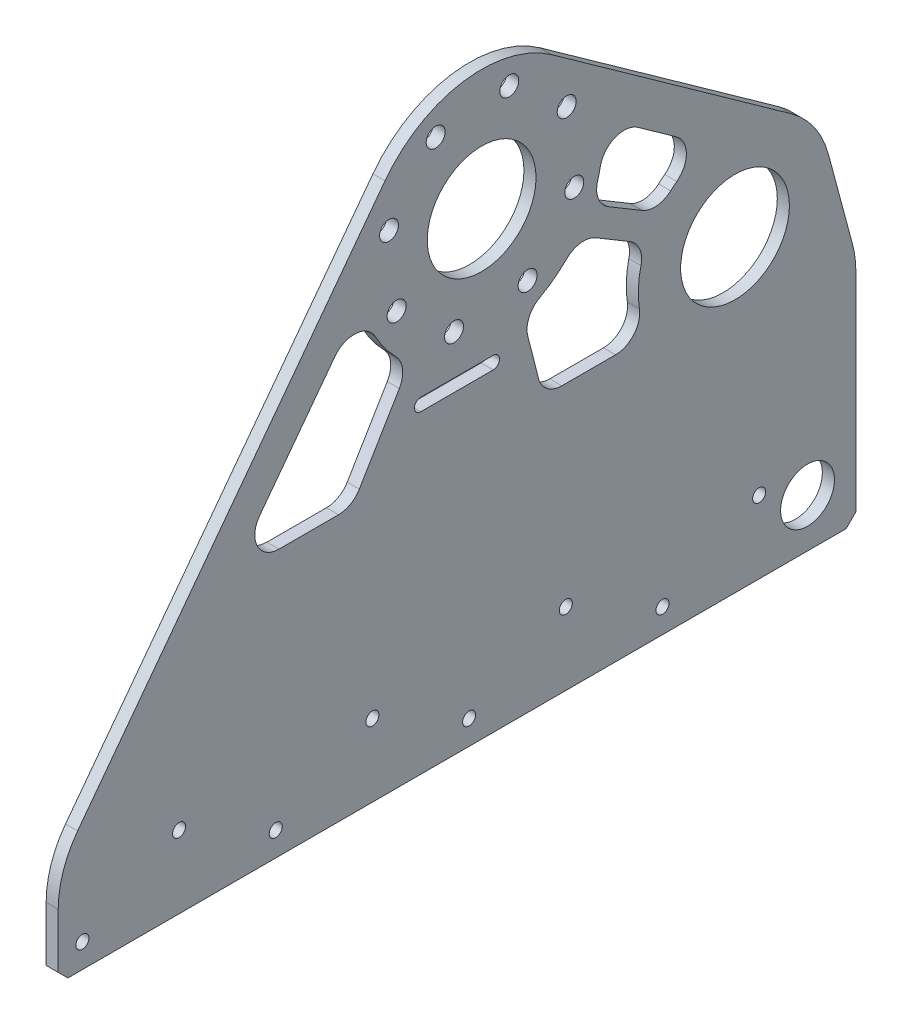
SolidWorks part; units mm, degrees
material "6061-T6 (SS)"
ref_plane "Front Plane" through (0, 0, 0) normal (0, 0, 1) x (1, 0, 0)
ref_plane "Top Plane" through (0, 0, 0) normal (0, 1, 0) x (1, 0, 0)
ref_plane "Right Plane" through (0, 0, 0) normal (1, 0, 0) x (0, 0, -1)
sketch "Sketch1" plane through (0, 0, 0) normal (1, 0, 0) x (0, 0, -1)
  line L0 (0, -25.4) -> (0, 31.864)
  line L13 (-209.55, -25.4) -> (0, -25.4)
  line L14 (-209.55, -25.4) -> (-209.55, -8.4756)
  line L15 (-204.4603, 6.7773) -> (-123.6994, 114.3161)
  line L16 (-209.55, 0) -> (0, 0) construction
  line L17 (-7.2155, 62.1365) -> (-0.8655, 38.438)
  line L18 (-79.8716, 121.0963) -> (-16.9981, 76.2396)
  circle A5 centre (-31.75, 55.5625) radius 14.2875
  circle A6 centre (-98.3115, 95.25) radius 14.2875 construction
  arc A7 (-79.8716, 121.0963) -> (-123.6994, 114.3161) centre (-98.3115, 95.25) ccw
  arc A8 (-16.9981, 76.2396) -> (-7.2155, 62.1365) centre (-31.75, 55.5625) cw
  circle A9 centre (-98.3115, 95.25) radius 14.2875
  arc A10 (-209.55, -8.4756) -> (-204.4603, 6.7773) centre (-184.15, -8.4756) cw
  arc A11 (-0.8655, 38.438) -> (0, 31.864) centre (-25.4, 31.864) cw
  point P4 (0, 0)
  dimension "D4" = 31.75
  dimension "D7" = 25.4
  dimension "D10" = 28.575
  dimension "D3" = 41.275
  dimension "D9" = 25.4
  dimension "D12" = 77.4954
  dimension "D13" = 63.5
  dimension "D14" = 63.5
  dimension "D5" = 25.4
  dimension "D8" = 28.575
  dimension "D2" = 15
  dimension "D6" = 209.55
extrude "Boss-Extrude1" add sketch "Sketch1" along normal blind 3.175
hole_wizard "#10 Clearance Hole1" positions "Sketch2" profile "Sketch3" hole size "#10" standard "ANSI Inch" end condition through all
sketch "Sketch2" plane through (3.175, 0, 0) normal (1, 0, 0) x (0, 0, -1)
  line L0 (-98.3115, 95.25) -> (-31.75, 55.5625) construction
  line L1 (-72.9115, 95.25) -> (-86.2351, 72.9046) construction
  circle A0 centre (-98.3115, 95.25) radius 25.4 construction
  circle A1 centre (-31.75, 55.5625) radius 14.2875 construction
  point P17 (-91.0503, 119.59)
  point P38 (-75.9661, 107.3265)
  point P39 (-73.9716, 87.9887)
  point P40 (-86.2351, 72.9046)
  point P41 (-105.5728, 70.91)
  point P42 (-120.657, 83.1735)
  point P43 (-122.6515, 102.5113)
  point P44 (-110.388, 117.5954)
  dimension "D1" = 50.8
  dimension "D2" = 8
sketch "Sketch3" plane through (3.175, 119.59, 91.0503) normal (0, 1, 0) x (0, 0, -1)
  line L0 (0, 0) -> (0, 3.175)
  line L1 (0, 3.175) -> (2.4892, 3.175)
  line L2 (2.4892, 3.175) -> (2.4892, 0)
  line L5 (2.4892, 0) -> (0, 0)
  line L11 (0, -6.35) -> (0, 107.95) construction
  dimension "Thru Hole Dia." = 4.9784
  dimension "Thru Hole Depth" = 3.175
sketch "Sketch9" plane through (3.175, 0, 0) normal (1, 0, 0) x (0, 0, -1)
  line L0 (0, 0) -> (-208.0942, 0) construction
  line L1 (0, -25.4) -> (0, 31.864) construction
  line L2 (0, -25.4) -> (0, 31.864) construction
  line L3 (-209.55, -25.4) -> (0, -25.4) construction
  line L4 (-164.2565, 44.45) -> (-129.699, 90.4657)
  line L5 (-123.6994, 114.3161) -> (-204.4603, 6.7773) construction
  line L6 (-176.1684, 44.45) -> (-132.2977, 44.45) construction
  line L7 (-164.2565, 44.45) -> (-132.2977, 44.45)
  line L8 (-66.9456, 100.1737) -> (-38.6711, 80.0014)
  line L9 (-16.9981, 76.2396) -> (-79.8716, 121.0963) construction
  line L10 (-69.5519, 81.7985) -> (-51.7692, 71.1955)
  line L11 (-55.0212, 65.7415) -> (-72.8039, 76.3444)
  line L12 (-98.3115, 95.25) -> (-31.75, 55.5625) construction
  line L13 (-98.3115, 95.25) -> (-132.7027, 37.5711) construction
  line L14 (-98.3115, 95.25) -> (-81.8784, 30.2801) construction
  line L15 (-117.2171, 69.7423) -> (-132.2977, 44.45)
  line L16 (-124.9046, 44.45) -> (-111.763, 66.4903) construction
  line L17 (-93.6431, 63.8451) -> (-88.7375, 44.45) construction
  line L18 (-82.1875, 44.45) -> (-87.487, 65.4022)
  line L19 (-82.1875, 44.45) -> (0, 44.45) construction
  line L20 (-82.1875, 44.45) -> (-54.5901, 44.45)
  line L21 (-124.9046, 44.45) -> (-88.7375, 44.45) construction
  line L22 (-124.9046, 44.45) -> (-88.7375, 44.45) construction
  circle A0 centre (-12.7, -12.7) radius 7.0739
  arc A2 (-204.4603, 6.7773) -> (-209.55, -8.4756) centre (-184.15, -8.4756) ccw construction
  arc A3 (-69.5519, 81.7985) -> (-117.2171, 69.7423) centre (-98.3115, 95.25) ccw construction
  arc A4 (-79.8716, 121.0963) -> (-123.6994, 114.3161) centre (-98.3115, 95.25) ccw construction
  arc A5 (-55.0212, 65.7415) -> (-51.7692, 71.1955) centre (-31.75, 55.5625) ccw construction
  arc A6 (-7.2155, 62.1365) -> (-16.9981, 76.2396) centre (-31.75, 55.5625) ccw construction
  arc A7 (-129.699, 90.4657) -> (-117.2171, 69.7423) centre (-98.3115, 95.25) ccw
  arc A8 (-54.5901, 44.45) -> (-55.0212, 65.7415) centre (-31.75, 55.5625) cw
  arc A9 (-51.7692, 71.1955) -> (-38.6711, 80.0014) centre (-31.75, 55.5625) cw
  arc A10 (-69.5519, 81.7985) -> (-66.9456, 100.1737) centre (-98.3115, 95.25) ccw
  arc A11 (-87.487, 65.4022) -> (-72.8039, 76.3444) centre (-98.3115, 95.25) ccw construction
  arc A12 (-87.487, 65.4022) -> (-72.8039, 76.3444) centre (-98.3115, 95.25) ccw
  arc A13 (-111.763, 66.4903) -> (-93.6431, 63.8451) centre (-98.3115, 95.25) ccw construction
  arc A14 (-111.763, 66.4903) -> (-93.6431, 63.8451) centre (-98.3115, 95.25) ccw construction
  dimension "D1" = 14.1478
  dimension "D3" = 12.7
  dimension "D2" = 12.7
  dimension "D4" = 9.525
  dimension "D5" = 44.45
  dimension "D6" = 9.525
  dimension "D7" = 6.35
  dimension "D8" = 6.35
  dimension "D9" = 6.35
  dimension "D10" = 45
  dimension "D11" = 45
extrude "Cut-Extrude1" cut sketch "Sketch9" against normal through all
fillet "Fillet1" radius 6.35 13 edges at (1.5875, 100.1737, 66.9456) (1.5875, 71.1955, 51.7692) (1.5875, 81.7985, 69.5519) (1.5875, 80.0014, 38.6711) (1.5875, 76.3444, 72.8039) (1.5875, 65.7415, 55.0212) (1.5875, 44.45, 82.1875) (1.5875, 65.4022, 87.487) (1.5875, 44.45, 54.5901) (1.5875, 44.45, 164.2565) (1.5875, 90.4657, 129.699) (1.5875, 69.7423, 117.2171) (1.5875, 44.45, 132.2977)
hole_wizard "1/8 (0.135) Diameter Hole1" positions "Sketch10" profile "Sketch11" hole size "1/8" standard "ANSI Inch" end condition through all
sketch "Sketch10" plane through (3.175, 0, 0) normal (1, 0, 0) x (0, 0, -1)
  point P4 (-177.8, -6.35)
  point P7 (-152.4, -19.05)
  point P10 (-127, -6.35)
  point P13 (-101.6, -19.05)
  point P16 (-76.2, -6.35)
  point P19 (-50.8, -19.05)
  point P22 (-25.4, -6.35)
  point P26 (-203.2, -19.05)
sketch "Sketch11" plane through (3.175, -6.35, 177.8) normal (0, 1, 0) x (0, 0, -1)
  line L0 (0, 0) -> (0, 3.175)
  line L1 (0, 3.175) -> (1.7145, 3.175)
  line L2 (1.7145, 3.175) -> (1.7145, 0)
  line L5 (1.7145, 0) -> (0, 0)
  line L11 (0, -6.35) -> (0, 107.95) construction
  dimension "Thru Hole Dia." = 3.429
  dimension "Thru Hole Depth" = 3.175
chamfer "Chamfer1" distance 2.54 angle 45 2 edges at (1.5875, -25.4, 0) (1.5875, -25.4, 209.55)
sketch "Sketch12" plane through (3.175, 0, 0) normal (1, 0, 0) x (0, 0, -1)
  line L0 (-53.34, 60.325) -> (-95.265, 60.325) construction
  line L6 (-114.315, 58.7375) -> (-95.265, 58.7375) construction
  line L8 (-114.315, 60.3885) -> (-95.265, 60.3885)
  line L10 (-96.5799, 60.325) -> (-86.2025, 60.325) construction
  line L11 (-114.315, 57.0865) -> (-95.265, 57.0865)
  line L12 (-95.265, 60.325) -> (-95.265, 57.15) construction
  line L13 (-341.2998, 60.325) -> (-114.315, 60.325) construction
  line L14 (-341.2998, 57.15) -> (-114.315, 57.15) construction
  line L15 (-114.315, 58.7375) -> (-123.7788, 58.7375) construction
  line L16 (-130.4505, 47.548) -> (-119.931, 65.1907) construction
  line L17 (-95.265, 58.7375) -> (-85.8013, 58.7375) construction
  line L18 (-86.1876, 60.2647) -> (-83.3998, 49.2429) construction
  arc A0 (-83.0781, 67.3931) -> (-86.1876, 60.2647) centre (-80.0314, 61.8218) ccw construction
  arc A3 (-114.315, 60.3885) -> (-114.315, 57.0865) centre (-114.315, 58.7375) ccw
  arc A4 (-95.265, 57.0865) -> (-95.265, 60.3885) centre (-95.265, 58.7375) ccw
  point P3 (-104.79, 58.7375)
  dimension "D1" = 3.302
  dimension "D2" = 19.05
extrude "Cut-Extrude2" cut sketch "Sketch12" against normal through all
